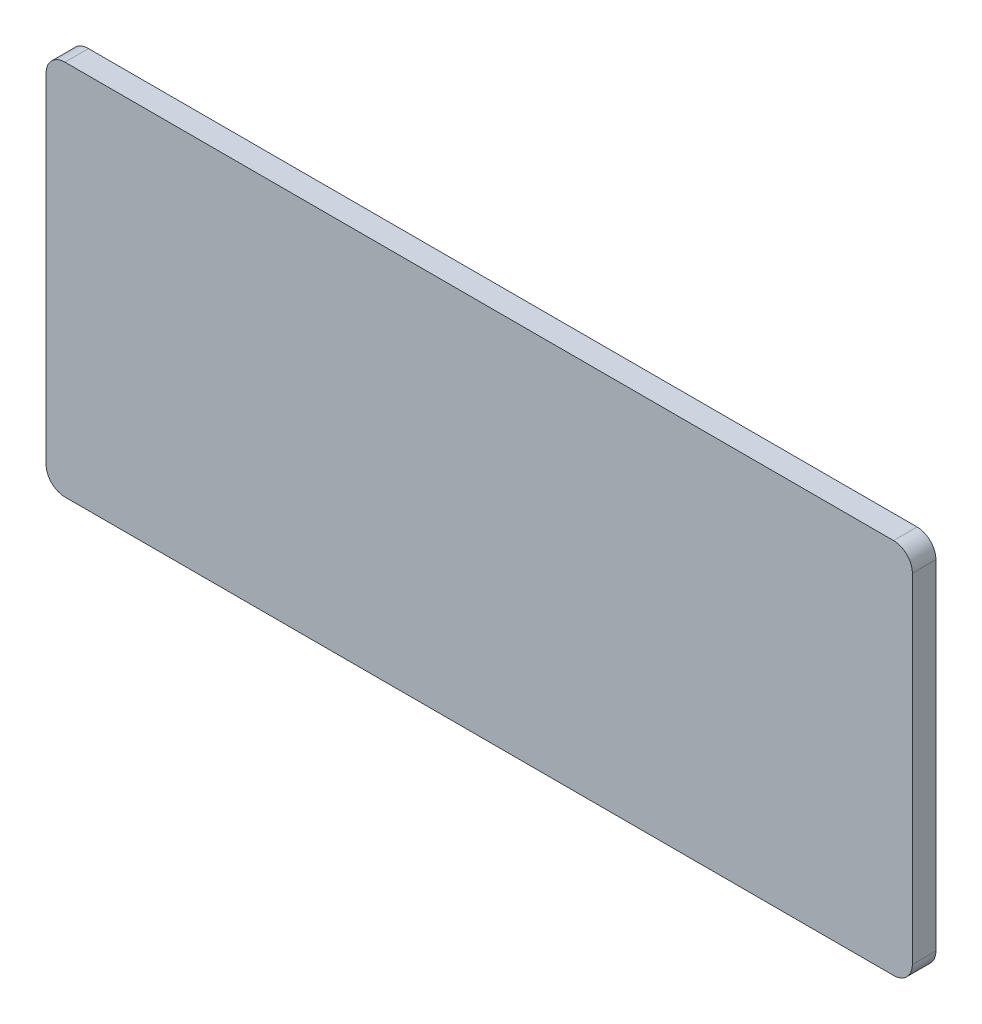
SolidWorks part; units mm, degrees
material "Custom Plastic"
ref_plane "X-Y Datum" through (0, 0, 0) normal (0, 0, 1) x (1, 0, 0)
ref_plane "X-Z Datum" through (0, 0, 0) normal (0, 1, 0) x (1, 0, 0)
ref_plane "Y-Z Datum" through (0, 0, 0) normal (1, 0, 0) x (0, 0, -1)
sketch "Sketch1" plane through (0, 0, 0) normal (0, 0, 1) x (1, 0, 0)
  line L1 (-58.42, -25.4) -> (58.42, -25.4)
  line L2 (-58.42, -25.4) -> (-58.42, 25.4)
  line L3 (-58.42, 25.4) -> (58.42, 25.4)
  line L4 (58.42, -25.4) -> (58.42, 25.4)
  line L5 (-58.42, -25.4) -> (58.42, 25.4) construction
  line L6 (-58.42, 25.4) -> (58.42, -25.4) construction
  point P0 (0, 0)
  dimension "D1" = 50.8
  dimension "D2" = 116.84
extrude "Boss-Extrude1" add sketch "Sketch1" along normal blind 3.175
fillet "Fillet1" radius 2.54 4 edges at (-58.42, -25.4, 1.5875) (-58.42, 25.4, 1.5875) (58.42, -25.4, 1.5875) (58.42, 25.4, 1.5875)
